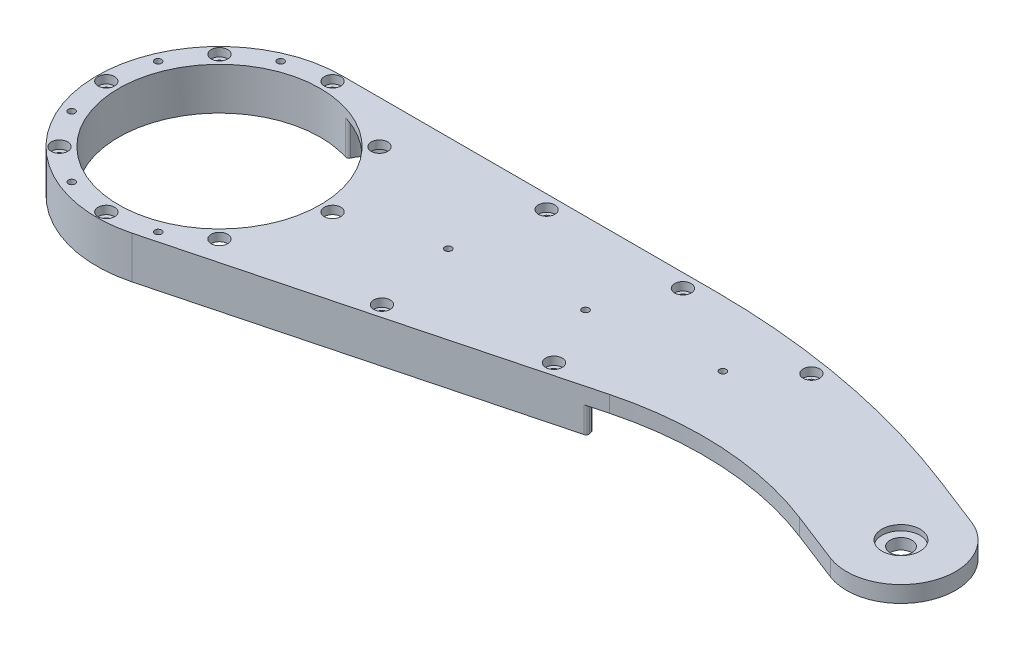
SolidWorks part; units mm, degrees
ref_plane "Спереди" through (0, 0, 0) normal (0, 0, 1) x (1, 0, 0)
ref_plane "Сверху" through (0, 0, 0) normal (0, 1, 0) x (1, 0, 0)
ref_plane "Справа" through (0, 0, 0) normal (1, 0, 0) x (0, 0, -1)
ref_plane "Плоскость4" through (0, 6, 0) normal (0, 1, 0) x (1, 0, 0)
sketch "Эскиз1" plane through (0, 6, 0) normal (0, 1, 0) x (1, 0, 0)
  line L0 (11.3988, -43.5324) -> (187.8755, 2.6774)
  line L1 (187.8755, 2.6774) -> (242.7579, -18.6427)
  line L2 (257.2421, 18.6427) -> (238.5994, 25.8849)
  line L3 (136.6047, 45) -> (0, 45)
  arc A0 (0, 45) -> (11.3988, -43.5324) centre (0, 0) ccw
  arc A1 (242.7579, -18.6427) -> (257.2421, 18.6427) centre (250, 0) ccw
  arc A2 (238.5994, 25.8849) -> (136.6047, 45) centre (136.6047, -236.6697) ccw
extrude "Бобышка-Вытянуть1" add sketch "Эскиз1" against normal blind 6
sketch "Эскиз2" plane through (0, 6, 0) normal (0, 1, 0) x (-1, 0, 0)
  line L0 (-118.5109, -42) -> (-21.4068, -42)
  line L1 (-31.3475, 35.2077) -> (-143.0826, 5.9503)
  line L2 (-143.0826, 5.9503) -> (-143.8426, 8.8524)
  line L3 (-143.8426, 8.8524) -> (-11.3988, 43.5324)
  line L4 (0, -45) -> (-136.6047, -45)
  line L5 (-211.069, -33.2121) -> (-207.1483, -30.9537)
  arc A0 (-21.4068, -42) -> (-11.8803, -35.0408) centre (-21.4068, -32) ccw
  arc A1 (-11.8803, -35.0408) -> (-20.3689, 30.8886) centre (0, 0) cw
  arc A2 (-20.3689, 30.8886) -> (-31.3475, 35.2077) centre (-28.8144, 25.5339) ccw
  arc A3 (-11.3988, 43.5324) -> (0, -45) centre (0, 0) cw
  arc A4 (-136.6047, -45) -> (-210.8334, -35.0433) centre (-136.6047, 236.6697) cw
  arc A5 (-210.8334, -35.0433) -> (-211.069, -33.2121) centre (-210.5698, -34.0786) cw
  arc A6 (-207.1483, -30.9537) -> (-200.8795, -34.4863) centre (-197.8811, -21.8368) ccw
  arc A7 (-200.8795, -34.4863) -> (-141.6391, -41.9545) centre (-136.6047, 236.6697) ccw
  arc A8 (-141.6391, -41.9545) -> (-133.2738, -37.7018) centre (-141.4585, -31.9562) ccw
  arc A9 (-133.2738, -37.7018) -> (-126.7174, -37.7143) centre (-130, -40) cw
  arc A10 (-126.7174, -37.7143) -> (-118.5109, -42) centre (-118.5109, -32) ccw
extrude "Бобышка-Вытянуть2" add sketch "Эскиз2" along normal blind 9.5
sketch "Эскиз3" plane through (0, 6, 0) normal (0, 1, 0) x (-1, 0, 0)
  line L0 (-118.5109, -42) -> (-21.4068, -42)
  line L1 (-31.3475, 35.2077) -> (-201.1741, -9.2608)
  arc A0 (-21.4068, -42) -> (-11.8803, -35.0408) centre (-21.4068, -32) ccw
  arc A1 (-11.8803, -35.0408) -> (-20.3689, 30.8886) centre (0, 0) cw
  arc A2 (-20.3689, 30.8886) -> (-31.3475, 35.2077) centre (-28.8144, 25.5339) ccw
  arc A3 (-201.1741, -9.2608) -> (-200.8795, -34.4863) centre (-197.8811, -21.8368) ccw
  arc A4 (-200.8795, -34.4863) -> (-141.6391, -41.9545) centre (-136.6047, 236.6697) ccw
  arc A5 (-141.6391, -41.9545) -> (-133.2738, -37.7018) centre (-141.4585, -31.9562) ccw
  arc A6 (-133.2738, -37.7018) -> (-126.7174, -37.7143) centre (-130, -40) cw
  arc A7 (-126.7174, -37.7143) -> (-118.5109, -42) centre (-118.5109, -32) ccw
extrude "Вырез-Вытянуть1" cut sketch "Эскиз3" against normal blind 3
sketch "Эскиз4" plane through (0, 3, 0) normal (0, 1, 0) x (-1, 0, 0)
  line L0 (-68.5109, -42) -> (-91.4891, -42)
  arc A0 (-83.2826, -37.7143) -> (-76.7174, -37.7143) centre (-80, -40) cw
  arc A1 (-76.7174, -37.7143) -> (-68.5109, -42) centre (-68.5109, -32) ccw
  arc A2 (-91.4891, -42) -> (-83.2826, -37.7143) centre (-91.4891, -32) ccw
extrude "Бобышка-Вытянуть3" add sketch "Эскиз4" along normal blind 12.5
sketch "Эскиз5" plane through (0, 3, 0) normal (0, 1, 0) x (-1, 0, 0)
  arc A0 (-183.4802, -33.6307) -> (-177.0946, -34.6607) centre (-180.6622, -36.4696) cw
  arc A1 (-177.0946, -34.6607) -> (-169.3505, -40.0694) centre (-168.1755, -30.1387) ccw
  arc A2 (-169.3505, -40.0694) -> (-192.5321, -36.3302) centre (-136.6047, 236.6697) cw
  arc A3 (-192.5321, -36.3302) -> (-183.4802, -33.6307) centre (-190.5252, -26.5336) ccw
extrude "Бобышка-Вытянуть4" add sketch "Эскиз5" along normal blind 12.5
sketch "Эскиз6" plane through (0, 3, 0) normal (0, 1, 0) x (-1, 0, 0)
  line L0 (-141.621, 6.333) -> (-119.3922, 12.1535)
  arc A0 (-126.2455, 5.9288) -> (-132.5966, 4.2658) centre (-130, 7.3085) cw
  arc A1 (-132.5966, 4.2658) -> (-141.621, 6.333) centre (-139.088, -3.3409) ccw
  arc A2 (-119.3922, 12.1535) -> (-126.2455, 5.9288) centre (-116.8591, 2.4797) ccw
extrude "Бобышка-Вытянуть5" add sketch "Эскиз6" along normal blind 12.5
sketch "Эскиз7" plane through (0, 3, 0) normal (0, 1, 0) x (-1, 0, 0)
  line L0 (-91.621, 19.4253) -> (-69.3922, 25.2459)
  arc A0 (-76.2455, 19.0212) -> (-82.5966, 17.3581) centre (-80, 20.4008) cw
  arc A1 (-82.5966, 17.3581) -> (-91.621, 19.4253) centre (-89.088, 9.7515) ccw
  arc A2 (-69.3922, 25.2459) -> (-76.2455, 19.0212) centre (-66.8591, 15.572) ccw
extrude "Бобышка-Вытянуть6" add sketch "Эскиз7" along normal blind 12.5
sketch "Эскиз8" plane through (0, 0, 0) normal (0, 0, 1) x (1, 0, 0)
  line L0 (37, 15.5) -> (0, 15.5)
  line L1 (0, 15.5) -> (0, 0)
  line L2 (0, 0) -> (37, 0)
  line L3 (37, 0) -> (37, 15.5)
  line L4 (0, 15.5) -> (0, 0) construction
revolve "Вырез-Повернуть1" cut sketch "Эскиз8" angle 360 about L4 reverse direction yes
hole_wizard "Диаметр отверстия Ø2.5 (2.5)1" positions "Эскиз10" profile "Эскиз9" hole size "Ø2.5" standard "Ansi Metric"
sketch "Эскиз10" plane through (0, 0, 0) normal (0, -1, 0) x (-1, 0, 0)
  point P0 (38.341, 15.8814)
  point P1 (38.341, -15.8814)
  point P2 (15.8814, -38.341)
  point P3 (-15.8814, -38.341)
  point P4 (15.8814, 38.341)
sketch "Эскиз9" plane through (-38.341, 0, -15.8814) normal (1, 0, 0) x (0, 0, -1)
  line L0 (0, 0) -> (0, 15.5)
  line L1 (0, 15.5) -> (1.25, 15.5)
  line L2 (1.25, 15.5) -> (1.25, 0)
  line L5 (1.25, 0) -> (0, 0)
  line L11 (0, -6.35) -> (0, 107.95) construction
  dimension "Диаметр сквозного отверстия" = 2.5
  dimension "Глубина сквозного отверстия" = 15.5
hole_wizard "Диаметр отверстия Ø2.5 (2.5)2" positions "Эскиз12" profile "Эскиз11" hole size "Ø2.5" standard "Ansi Metric"
sketch "Эскиз12" plane through (0, 0, 0) normal (0, -1, 0) x (-1, 0, 0)
  point P0 (-163.6626, 20.9657)
  point P1 (-119.0273, 15.2478)
  point P2 (-74.3921, 9.5298)
sketch "Эскиз11" plane through (163.6626, 0, -20.9657) normal (1, 0, 0) x (0, 0, -1)
  line L0 (0, 0) -> (0, 15.5)
  line L1 (0, 15.5) -> (1.25, 15.5)
  line L2 (1.25, 15.5) -> (1.25, 0)
  line L5 (1.25, 0) -> (0, 0)
  line L11 (0, -6.35) -> (0, 107.95) construction
  dimension "Диаметр сквозного отверстия" = 2.5
  dimension "Глубина сквозного отверстия" = 15.5
hole_wizard "Цековка для винта с заклепочной головкой M31" positions "Эскиз14" profile "Эскиз13" counterbore size "M3" standard "Ansi Metric"
sketch "Эскиз14" plane through (0, 0, 0) normal (0, -1, 0) x (-1, 0, 0)
  point P0 (-130, 40)
  point P1 (-80, 40)
  point P2 (-80, -20.4008)
  point P3 (-130, -7.3085)
  point P4 (-180.6622, 36.4696)
sketch "Эскиз13" plane through (130, 0, -40) normal (1, 0, 0) x (0, 0, -1)
  line L0 (0, 0) -> (0, 15.5)
  line L1 (0, 15.5) -> (1.7, 15.5)
  line L3 (1.7, 15.5) -> (1.7, 3)
  line L4 (1.7, 3) -> (3.025, 3)
  line L5 (3.025, 3) -> (3.025, 0)
  line L7 (3.025, 0) -> (0, 0)
  line L11 (0, -6.35) -> (0, 107.95) construction
  dimension "Диаметр сквозного отверстия" = 3.4
  dimension "Глубина сквозного отверстия" = 15.5
  dimension "Диаметр цековки" = 6.05
  dimension "Глубина цековки" = 3
hole_wizard "Цековка для винта с заклепочной головкой M32" positions "Эскиз16" profile "Эскиз15" counterbore size "M3" standard "Ansi Metric"
sketch "Эскиз16" plane through (0, 0, 0) normal (0, -1, 0) x (-1, 0, 0)
  point P0 (29.3449, 29.3449)
  point P1 (0, 41.5)
  point P2 (0, -41.5)
  point P3 (29.3449, -29.3449)
  point P4 (41.5, 0)
sketch "Эскиз15" plane through (-29.3449, 0, -29.3449) normal (1, 0, 0) x (0, 0, -1)
  line L0 (0, 0) -> (0, 15.5)
  line L1 (0, 15.5) -> (1.6, 15.5)
  line L3 (1.6, 15.5) -> (1.6, 3)
  line L4 (1.6, 3) -> (3.025, 3)
  line L5 (3.025, 3) -> (3.025, 0)
  line L7 (3.025, 0) -> (0, 0)
  line L11 (0, -6.35) -> (0, 107.95) construction
  dimension "Диаметр сквозного отверстия" = 3.2
  dimension "Глубина сквозного отверстия" = 15.5
  dimension "Диаметр цековки" = 6.05
  dimension "Глубина цековки" = 3
hole_wizard "Отверстие1" positions "Эскиз18" profile "Эскиз17" legacy
sketch "Эскиз18" plane through (0, 3, 0) normal (0, 1, 0) x (1, 0, 0)
  point P0 (29.3449, -29.3449)
  point P1 (29.3449, 29.3449)
  point P2 (41.5, 0)
sketch "Эскиз17" plane through (29.3449, 3, 29.3449) normal (1, 0, 0) x (0, 0, 1)
  line L0 (0, 0) -> (0, 3)
  line L1 (0, 3) -> (3.025, 3)
  line L2 (3.025, 3) -> (3.025, 0)
  line L3 (3.025, 0) -> (0, 0)
  line L4 (0, 110) -> (0, -10) construction
  dimension "Диаметр" = 6.05
  dimension "Глубина" = 3
hole_wizard "Отверстие обработанное метчиком M14x1.51" positions "Эскиз20" profile "Эскиз19" tap size "M14x1.5" standard "Ansi Metric"
sketch "Эскиз20" plane through (0, 0, 0) normal (0, -1, 0) x (-1, 0, 0)
  point P0 (-250, 0)
sketch "Эскиз19" plane through (250, 0, 0) normal (1, 0, 0) x (0, 0, -1)
  line L0 (0, 0) -> (0, 15.5)
  line L1 (0, 15.5) -> (4, 15.5)
  line L3 (4, 15.5) -> (4, 2)
  line L4 (4, 2) -> (7, 2)
  line L5 (7, 2) -> (7, 0)
  line L7 (7, 0) -> (0, 0)
  line L11 (0, -6.35) -> (0, 107.95) construction
  dimension "Диаметр проходного сверла" = 8
  dimension "Глубина проходного сверла" = 15.5
  dimension "Диаметр резьбы" = 14
  dimension "Глубина резьбы" = 2
fillet "Скругление1" radius 1 5 edges at (143.8426, 10.75, 8.8524) (11.8803, 9.25, -35.0408) (207.1483, 10.75, -30.9537) (20.3689, 9.25, 30.8886) (143.0826, 10.75, 5.9503) tangent propagation no
fillet "Скругление2" radius 120 1 edges at (187.8755, 3, -2.6774) tangent propagation no
mirror "Зеркальное отражение1" about plane through (0, 0, 0) normal (0, 1, 0) of bodies 116
delete or keep bodies "Тело-Удалить/Сохранить 1" type delete bodies bodies 116
